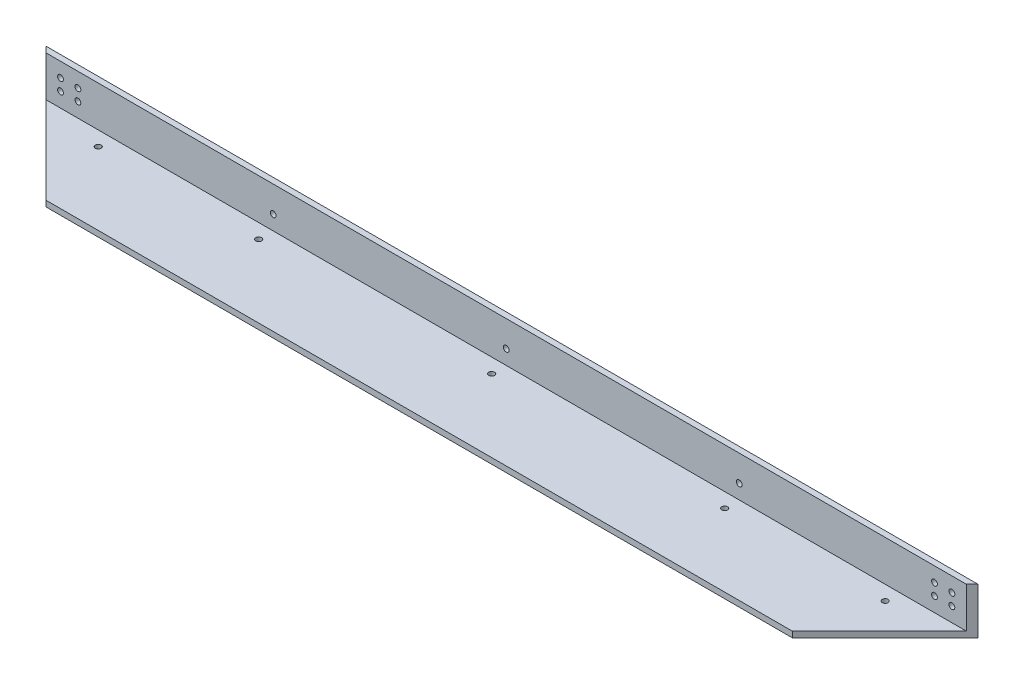
SolidWorks part; units mm, degrees
ref_plane "Front Plane" through (0, 0, 0) normal (0, 0, 1) x (1, 0, 0)
ref_plane "Top Plane" through (0, 0, 0) normal (0, 1, 0) x (1, 0, 0)
ref_plane "Right Plane" through (0, 0, 0) normal (1, 0, 0) x (0, 0, -1)
sketch "Sketch1" plane through (0, 0, 0) normal (1, 0, 0) x (0, 0, -1)
  line L0 (0, 0) -> (-50.8, 0)
  line L1 (-50.8, 0) -> (-50.8, 3.175)
  line L2 (-50.8, 3.175) -> (-3.175, 3.175)
  line L3 (-3.175, 3.175) -> (-3.175, 25.4)
  line L4 (-3.175, 25.4) -> (0, 25.4)
  line L5 (0, 25.4) -> (0, 0)
  dimension "LHeight" = 25.4
  dimension "LWidth" = 50.8
  dimension "LMaterialThickness" = 3.175
  dimension "D1" = 47.625
  dimension "D2" = 22.225
  dimension "D3" = 3.175
extrude "Boss-Extrude1" add sketch "Sketch1" along normal blind 510
chamfer "Chamfer6" distance 50.8 angle 45 1 edges at (510, 1.5875, 50.8)
chamfer "Chamfer7" distance 50.8 angle 45 1 edges at (0, 1.5875, 50.8)
sketch "BackSideHoles-Sketch2" plane through (0, 0, 0) normal (0, 0, -1) x (-1, 0, 0)
  line L0 (0, 0) -> (0, 25.4) construction
  line L1 (-510, 0) -> (0, 0) construction
  line L2 (-510, 0) -> (-510, 25.4) construction
  circle A0 centre (-498.8875, 17.4625) radius 1.5875
  circle A1 centre (-489.3625, 17.4625) radius 1.5875
  circle A2 centre (-20.6375, 17.4625) radius 1.5875
  circle A3 centre (-11.1125, 17.4625) radius 1.5875
  circle A4 centre (-11.1125, 11.1125) radius 1.5875
  circle A5 centre (-20.6375, 11.1125) radius 1.5875
  circle A6 centre (-489.3625, 11.1125) radius 1.5875
  circle A7 centre (-498.8875, 11.1125) radius 1.5875
  circle A8 centre (-382.5, 11.1125) radius 1.5875
  circle A9 centre (-255, 11.1125) radius 1.5875
  circle A10 centre (-127.5, 11.1125) radius 1.5875
  dimension "D5" = 3.175
  dimension "D1" = 11.1125
  dimension "D2" = 20.6375
  dimension "D3" = 11.1125
  dimension "D4" = 20.6375
  dimension "D6" = 7.9375
  dimension "D7" = 11.1125
  dimension "D8" = 127.5
  dimension "D9" = 127.5
  dimension "D10" = 127.5
sketch "BottomHoles-Sketch3" plane through (0, 0, 0) normal (0, -1, 0) x (1, 0, 0)
  line L0 (510, 0) -> (0, 0) construction
  circle A7 centre (39.6875, 11.1125) radius 1.5875
  circle A8 centre (470.3125, 11.1125) radius 1.5875
  circle A9 centre (127.5, 11.1125) radius 1.5875
  circle A10 centre (255, 11.1125) radius 1.5875
  circle A11 centre (382.5, 11.1125) radius 1.5875
  dimension "D5" = 3.175
  dimension "D2" = 39.6875
  dimension "D3" = 39.6875
  dimension "D4" = 11.1125
  dimension "D1" = 127.5
  dimension "D6" = 127.5
  dimension "D7" = 127.5
extrude "BottomHoles-Cut-Extrude1" cut sketch "BottomHoles-Sketch3" against normal through all
extrude "BackSideHoles-Cut-Extrude2" cut sketch "BackSideHoles-Sketch2" against normal through all
equation "\"LowerRailWidth\"= 2.00in"
equation "\"LowerRailHeight\"= 1.00in"
equation "\"RailThickness\"= .125in'Spec"
equation "\"SideRailHoleX1FromSide\"= \"HoleOffsetFromSide\""
equation "\"SideRailHoleX2FromSide\"= \"VSWidth\" - \"HoleOffsetFromEdge\" - \"RailThickness\"'Equals 20.6375"
equation "\"SideRailHoleY1FromEdge\"= \"HoleOffsetFromEdge\""
equation "\"FrontBackRailLength\"= 510mm"
equation "\"VSWidth\"= 1.25in'Spec"
equation "\"HoleOffsetFromEdge\"= \"RailThickness\" * 2.5"
equation "\"HoleOffsetFromSide\"= \"RailThickness\" * 3.5"
equation "\"SideRailHoleY2FromSide\"= \"HoleOffsetFromSide\""
equation "\"FasteningHoleDiameter\"= .125in"
equation "\"D1@Boss-Extrude1\"=\"FrontBackRailLength\""
equation "\"D1@Chamfer6\"=\"LowerRailWidth\""
equation "\"D1@Chamfer7\"=\"LowerRailWidth\""
equation "\"D1@BackSideHoles-Sketch2\" = \"SideRailHoleX1FromSide\""
equation "\"D2@BackSideHoles-Sketch2\" = \"SideRailHoleX2FromSide\""
equation "\"D3@BackSideHoles-Sketch2\" = \"SideRailHoleX1FromSide\""
equation "\"D4@BackSideHoles-Sketch2\" = \"SideRailHoleX2FromSide\""
equation "\"D5@BackSideHoles-Sketch2\" = \"FasteningHoleDiameter\""
equation "\"D6@BackSideHoles-Sketch2\" = \"SideRailHoleY1FromEdge\""
equation "\"D7@BackSideHoles-Sketch2\" = \"SideRailHoleY2FromSide\""
equation "\"LHeight@Sketch1\"=\"LowerRailHeight\""
equation "\"LWidth@Sketch1\"=\"LowerRailWidth\""
equation "\"24vPSUMountingHoleDistanceFromEdge\"= 33.5mm"
equation "\"24vPSUMountingHoleDistance\"= 150mm"
equation "\"24vPSUMountingHoleDiameter\"= 2.5mm"
equation "\"LowerCornerBlockWidth\"= \"LowerRailWidth\" - \"RailThickness\" * 2'Room for left front stepper"
equation "\"D2@BottomHoles-Sketch3\"=\"LowerCornerBlockX1FromSide\""
equation "\"D3@BottomHoles-Sketch3\"=\"LowerCornerBlockX1FromSide\""
equation "\"D4@BottomHoles-Sketch3\"=\"LowerCornerBlockY1FromSide\""
equation "\"D5@BottomHoles-Sketch3\"=\"FasteningHoleDiameter\""
equation "\"LowerCornerBlockX1FromSide\"= \"LowerCornerBlockWidth\" - \"HoleOffsetFromEdge\" + \"RailThickness\""
equation "\"LowerCornerBlockY1FromSide\"= \"HoleOffsetFromSide\""
equation "\"FrontOrBackEnclosureOffsets\"= \"FrontBackRailLength\" / 4"
equation "\"D1@BottomHoles-Sketch3\"=\"FrontOrBackEnclosureOffsets\""
equation "\"D6@BottomHoles-Sketch3\"=\"FrontOrBackEnclosureOffsets\""
equation "\"D7@BottomHoles-Sketch3\"=\"FrontOrBackEnclosureOffsets\""
equation "\"D8@BackSideHoles-Sketch2\"=\"FrontOrBackEnclosureOffsets\""
equation "\"D9@BackSideHoles-Sketch2\"=\"FrontOrBackEnclosureOffsets\""
equation "\"D10@BackSideHoles-Sketch2\"=\"FrontOrBackEnclosureOffsets\""
